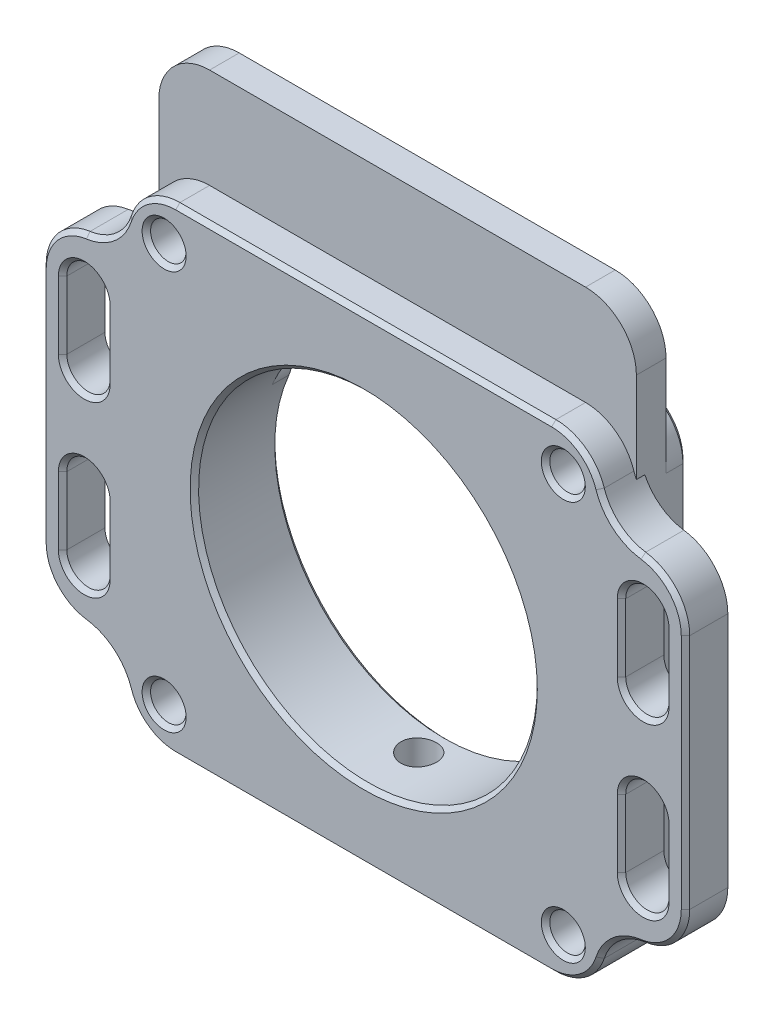
SolidWorks part; units mm, degrees
material "Alumina"
ref_plane "Plan de face" through (0, 0, 0) normal (0, 0, 1) x (1, 0, 0)
ref_plane "Plan de dessus" through (0, 0, 0) normal (0, 1, 0) x (1, 0, 0)
ref_plane "Plan de droite" through (0, 0, 0) normal (1, 0, 0) x (0, 0, -1)
sketch "Sketch1" plane through (0, 0, 0) normal (0, 0, 1) x (1, 0, 0)
  line L0 (-28.2, -20) -> (-38, -20)
  line L1 (28.2, -28.2) -> (-28.2, -28.2)
  line L2 (28.2, -28.2) -> (28.2, -20)
  line L3 (28.2, 28.2) -> (-28.2, 28.2)
  line L4 (-28.2, -28.2) -> (-28.2, -20)
  line L5 (-33, 6) -> (-33, 14) construction
  line L6 (33, -10) -> (-33, -10) construction
  line L7 (38, -20) -> (28.2, -20)
  line L8 (38, -20) -> (38, 20)
  line L9 (38, 20) -> (28.2, 20)
  line L10 (-38, -20) -> (-38, 20)
  line L11 (33, -10) -> (33, 10) construction
  line L12 (33, 10) -> (-33, 10) construction
  line L13 (-28.2, 20) -> (-28.2, 28.2)
  line L14 (-35.5592, 6) -> (-35.5592, 14)
  line L15 (-28.2, 20) -> (-38, 20)
  line L16 (-30.4408, 6) -> (-30.4408, 14)
  line L17 (-33, -6) -> (-33, -14) construction
  line L18 (-30.4408, -6) -> (-30.4408, -14)
  line L19 (28.2, 20) -> (28.2, 28.2)
  line L20 (-33, -10) -> (-33, 10) construction
  line L21 (33, -10) -> (-33, 10) construction
  line L22 (33, 10) -> (-33, -10) construction
  line L23 (-35.5592, -6) -> (-35.5592, -14)
  line L24 (33, -6) -> (33, -14) construction
  line L25 (35.5592, -6) -> (35.5592, -14)
  line L26 (30.4408, -6) -> (30.4408, -14)
  line L27 (33, 6) -> (33, 14) construction
  line L28 (30.4408, 6) -> (30.4408, 14)
  line L29 (35.5592, 6) -> (35.5592, 14)
  line L30 (0, 0) -> (0, -6) construction
  arc A0 (-35.5592, 6) -> (-30.4408, 6) centre (-33, 6) ccw
  arc A1 (-30.4408, 14) -> (-35.5592, 14) centre (-33, 14) ccw
  arc A2 (-30.4408, -6) -> (-35.5592, -6) centre (-33, -6) ccw
  arc A3 (-35.5592, -14) -> (-30.4408, -14) centre (-33, -14) ccw
  arc A4 (35.5592, -6) -> (30.4408, -6) centre (33, -6) ccw
  arc A5 (30.4408, -14) -> (35.5592, -14) centre (33, -14) ccw
  arc A6 (30.4408, 6) -> (35.5592, 6) centre (33, 6) ccw
  arc A7 (35.5592, 14) -> (30.4408, 14) centre (33, 14) ccw
  circle A8 centre (0, 0) radius 20
  point P0 (0, 0)
  point P5 (0, 0)
  point P14 (0, 0)
  point P22 (-33, 10)
  point P28 (-33, -10)
  point P35 (33, -10)
  point P42 (33, 10)
  dimension "D5" = 8
  dimension "D9" = 40
  dimension "D1" = 56.4
  dimension "D2" = 56.4
  dimension "D3" = 76
  dimension "D4" = 40
  dimension "D6" = 20
  dimension "D7" = 20
  dimension "D8" = 28.2
  dimension "D10" = 66
extrude "Boss-Extrude1" add sketch "Sketch1" along normal blind 10
fillet "Fillet1" radius 6 4 edges at (28.2, 28.2, 5) (-28.2, 28.2, 5) (-28.2, -28.2, 5) (28.2, -28.2, 5)
hole_wizard "Tap Drill for M5 Tap1" positions "Sketch2" profile "Sketch3" hole size "M5" standard "ISO" end condition through all
sketch "Sketch2" plane through (0, 0, 10) normal (0, 0, 1) x (1, 0, 0)
  line L1 (-23.57, 23.57) -> (23.57, 23.57) construction
  line L2 (-23.57, 23.57) -> (-23.57, -23.57) construction
  line L3 (-23.57, -23.57) -> (23.57, -23.57) construction
  line L4 (23.57, 23.57) -> (23.57, -23.57) construction
  line L5 (-23.57, 23.57) -> (23.57, -23.57) construction
  line L6 (-23.57, -23.57) -> (23.57, 23.57) construction
  point P1 (0, 0)
  point P2 (23.57, -23.57)
  point P5 (-23.57, 23.57)
  point P6 (-23.57, -23.57)
  point P7 (23.57, 23.57)
  dimension "D1" = 47.14
  dimension "D2" = 47.14
sketch "Sketch3" plane through (0, 0, 10) normal (1, 0, 0) x (0, -1, 0)
  line L0 (0, 0) -> (0, 10)
  line L1 (0, 10) -> (2.1, 10)
  line L2 (2.1, 10) -> (2.1, 0)
  line L5 (2.1, 0) -> (0, 0)
  line L11 (0, -6.35) -> (0, 107.95) construction
  dimension "Thru Hole Dia." = 4.2
  dimension "Thru Hole Depth" = 10
sketch "Sketch4" plane through (0, 0, 10) normal (0, 0, -1) x (-1, 0, 0)
  line L1 (28.2, -28.2) -> (-28.2, -28.2)
  line L2 (28.2, -28.2) -> (28.2, 28.2)
  line L3 (28.2, 28.2) -> (-28.2, 28.2)
  line L4 (-28.2, -28.2) -> (-28.2, 28.2)
  line L5 (28.2, -28.2) -> (-28.2, 28.2) construction
  line L6 (28.2, 28.2) -> (-28.2, -28.2) construction
  point P0 (0, 0)
extrude "Cut-Extrude2" cut sketch "Sketch4" along normal through all from offset 5 flip side to cut
fillet "Fillet2" radius 6 4 edges at (38, -20, 7.5) (38, 20, 7.5) (-38, -20, 7.5) (-38, 20, 7.5)
fillet "Fillet3" radius 6 4 edges at (-28.2, -20, 7.5) (-28.2, 20, 7.5) (28.2, 20, 7.5) (28.2, -20, 7.5)
hole_wizard "Tap Drill for M5 Tap2" positions "Sketch6" profile "Sketch8" hole size "M5" standard "ISO"
sketch "Sketch6" plane through (0, -28.2, 0) normal (0, -1, 0) x (-1, 0, 0)
  line L1 (22.2, -10) -> (-22.2, -10) construction
  point P0 (0, -3.5)
  dimension "D1" = 6.5
sketch "Sketch8" plane through (0, -28.2, 3.5) normal (1, 0, 0) x (0, 0, -1)
  line L0 (0, 0) -> (0, 21.2618)
  line L1 (0, 21.2618) -> (2.1, 20)
  line L2 (2.1, 20) -> (2.1, 0)
  line L5 (2.1, 0) -> (0, 0)
  line L10 (0, 21.2618) -> (-2.1, 20) construction
  line L11 (0, -6.35) -> (0, 107.95) construction
  dimension "Hole Dia." = 4.2
  dimension "Hole Depth" = 20
  dimension "Drill Angle" = 118
sketch "Sketch9" plane through (0, 0, 0) normal (0, 0, -1) x (-1, 0, 0)
  line L2 (-28.2, 22.2) -> (-28.2, 34)
  line L3 (-22.2, 40) -> (22.2, 40)
  line L4 (28.2, 22.2) -> (28.2, 34)
  line L5 (28.2, 22.2) -> (28.2, -22.2) construction
  line L6 (-22.2, 28.2) -> (22.2, 28.2) construction
  line L7 (-22.2, 28.2) -> (22.2, 28.2)
  arc A0 (28.2, 22.2) -> (22.2, 28.2) centre (22.2, 22.2) ccw construction
  arc A1 (-22.2, 28.2) -> (-28.2, 22.2) centre (-22.2, 22.2) ccw construction
  arc A2 (28.2, 22.2) -> (22.2, 28.2) centre (22.2, 22.2) ccw
  arc A3 (-22.2, 28.2) -> (-28.2, 22.2) centre (-22.2, 22.2) ccw
  arc A4 (22.2, 40) -> (28.2, 34) centre (22.2, 34) cw
  arc A5 (-28.2, 34) -> (-22.2, 40) centre (-22.2, 34) cw
  dimension "D2" = 6
  dimension "D1" = 40
extrude "Boss-Extrude2" add sketch "Sketch9" against normal blind 3.5 from offset 2.5 offset against normal yes
sketch "Sketch10" plane through (0, 0, 0) normal (0, 0, -1) x (-1, 0, 0)
  line L1 (-18, 0) -> (18, 0)
  line L2 (-18, 0) -> (-18, 49.8064)
  line L3 (-18, 49.8064) -> (18, 49.8064)
  line L4 (18, 0) -> (18, 49.8064)
  dimension "D1" = 36
  dimension "D2" = 18
extrude "Cut-Extrude3" cut sketch "Sketch10" against normal up to surface (2.5 mm away) up to face at (0, 31.7213, 2.5)
fillet "Fillet4" radius 4 4 edges at (-18, 28.2, 1.25) (18, 28.2, 1.25) (18, 8.7178, 1.25) (-18, 8.7178, 1.25)
chamfer "Chamfer1" distance 0.5 angle 45 57 edges at (-21.47, 23.57, 10) (25.67, 23.57, 10) (25.67, -23.57, 10) (-21.47, -23.57, 10) (-33, 3.4408, 10) (-30.4408, 10, 10) (-35.5592, 10, 10) (-33, 16.5592, 10) (-33, -16.5592, 10) (-30.4408, -10, 10) (-35.5592, -10, 10) (-33, -3.4408, 10) (33, -16.5592, 10) (35.5592, -10, 10) (30.4408, -10, 10) (33, -3.4408, 10) (33, 3.4408, 10) (35.5592, 10, 10) (30.4408, 10, 10) (33, 16.5592, 10) (25.67, -23.57, 0) (25.67, 23.57, 0) (-21.47, 23.57, 0) (-21.47, -23.57, 0) (18, 16.8958, 0) (18.0842, 8.7752, 0) (19.1716, 27.0284, 0) (0, -20, 0) (22.1, 28.2, 0) (-18.0842, 8.7752, 0) (26.4426, 26.4426, 0) (-18, 16.8958, 0) (28.2, 0, 0) (-19.1716, 27.0284, 0) (26.4426, -26.4426, 0) (-22.1, 28.2, 0) (0, -28.2, 0) (-26.4426, 26.4426, 0) (-26.4426, -26.4426, 0) (-28.2, 0, 0) (36.5197, -17.9462, 10) (38, 0, 10) (29.7681, -21.2887, 10) (36.5197, 17.9462, 10) (25.7305, -27.0513, 10) (29.7681, 21.2887, 10) (0, -28.2, 10) (25.7305, 27.0513, 10) (-25.7305, -27.0513, 10) (0, 28.2, 10) (-29.7681, -21.2887, 10) (-25.7305, 27.0513, 10) (-36.5197, -17.9462, 10) (-29.7681, 21.2887, 10) (-38, 0, 10) (-36.5197, 17.9462, 10) (20, 0, 10)
